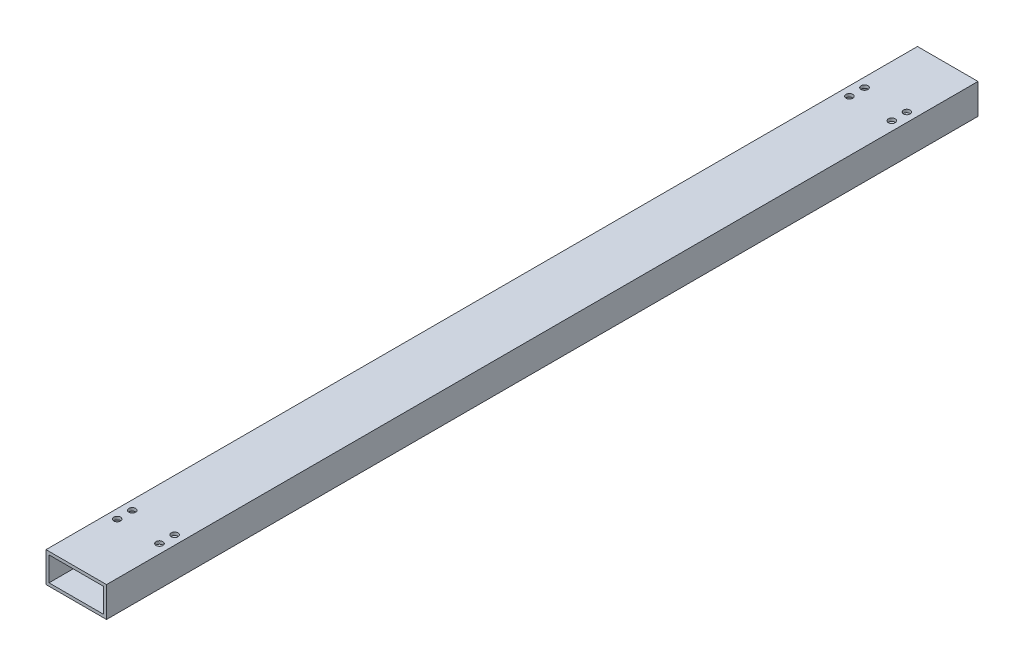
SolidWorks part; units mm, degrees
ref_plane "Front Plane" through (0, 0, 0) normal (0, 0, 1) x (1, 0, 0)
ref_plane "Top Plane" through (0, 0, 0) normal (0, 1, 0) x (1, 0, 0)
ref_plane "Right Plane" through (0, 0, 0) normal (1, 0, 0) x (0, 0, -1)
sketch "Sketch1" plane through (0, 0, 0) normal (0, 0, 1) x (1, 0, 0)
  line L0 (31.75, 0) -> (28.575, 0) construction
  line L1 (-31.75, 0) -> (31.75, 0) construction
  line L2 (0, 15.875) -> (0, -15.875)
  point P7 (0, 0)
  dimension "Width" = 63.5
  dimension "Wall Thickness" = 3.175
  dimension "Height" = 31.75
sketch "Sketch2" plane through (0, 0, 0) normal (1, 0, 0) x (0, 0, -1)
  line L0 (457.2, 0) -> (-457.2, 0)
  point P4 (0, 0)
  dimension "Length" = 914.4
sketch "Sketch3" plane through (0, 0, 0) normal (0, 0, 1) x (1, 0, 0)
  line L0 (0, 12.7) -> (0, 15.875) construction
  line L1 (-31.75, 15.875) -> (31.75, 15.875)
  line L2 (-31.75, 15.875) -> (-31.75, -15.875)
  line L3 (-31.75, -15.875) -> (31.75, -15.875)
  line L4 (31.75, 15.875) -> (31.75, -15.875)
  line L5 (-31.75, 15.875) -> (31.75, -15.875) construction
  line L6 (-31.75, -15.875) -> (31.75, 15.875) construction
  line L7 (-28.575, 12.7) -> (28.575, 12.7)
  line L8 (-28.575, 12.7) -> (-28.575, -12.7)
  line L9 (-28.575, -12.7) -> (28.575, -12.7)
  line L10 (28.575, 12.7) -> (28.575, -12.7)
  line L11 (-28.575, 12.7) -> (28.575, -12.7) construction
  line L12 (-28.575, -12.7) -> (28.575, 12.7) construction
  line L13 (31.75, 0) -> (28.575, 0) construction
  line L14 (31.75, 0) -> (28.575, 0) construction
  point P0 (0, 0)
  point P8 (0, 0)
extrude "Boss-Extrude1" add sketch "Sketch3" along normal up to vertex (457.2 mm away) and the other way up to vertex (457.2 mm away) up to point (0, 0, 457.2) other way up to point (0, 0, -457.2)
sketch "Sketch4" plane through (0, 0, 0) normal (0, 0, 1) x (1, 0, 0)
  line L0 (31.75, -15.875) -> (28.575, -15.875) construction
  line L1 (31.75, -15.875) -> (31.75, 15.875) construction
  line L2 (28.575, -12.7) -> (28.575, 12.7) construction
  line L3 (-31.75, -15.875) -> (31.75, -15.875) construction
sketch "Sketch5" plane through (0, -15.875, 0) normal (0, -1, 0) x (1, 0, 0)
  line L1 (-28.575, 384.175) -> (28.575, 384.175)
  line L2 (-28.575, 384.175) -> (-28.575, 400.05)
  line L3 (-28.575, 400.05) -> (28.575, 400.05)
  line L4 (28.575, 384.175) -> (28.575, 400.05)
  line L5 (-28.575, 384.175) -> (28.575, 400.05) construction
  line L6 (-28.575, 400.05) -> (28.575, 384.175) construction
  line L7 (-31.75, 457.2) -> (31.75, 457.2) construction
  line L8 (-31.75, 0) -> (31.75, 0) construction
  line L9 (-31.75, 457.2) -> (-31.75, -457.2) construction
  line L10 (31.75, 457.2) -> (31.75, -457.2) construction
  circle A0 centre (-22.225, 392.1125) radius 3.5719
  circle A1 centre (22.225, 392.1125) radius 3.5719
  circle A2 centre (22.225, -392.1125) radius 3.5719
  circle A3 centre (-22.225, -392.1125) radius 3.5719
  circle A4 centre (22.225, 376.2375) radius 3.5719
  circle A5 centre (-22.225, 376.2375) radius 3.5719
  circle A6 centre (22.225, -376.2375) radius 3.5719
  circle A7 centre (-22.225, -376.2375) radius 3.5719
  point P0 (0, 392.1125)
  dimension "D3" = 7.1437
  dimension "D4" = 7.1437
  dimension "D1" = 57.15
  dimension "D2" = 15.875
  dimension "D5" = 22.225
  dimension "D6" = 22.225
  dimension "D7" = 44.45
  dimension "D8" = 57.15
  dimension "D9" = 15.875
extrude "Cut-Extrude1" cut sketch "Sketch5" against normal through all contours A0 | A1 | A3 | A2 | A7 | A6 | A4 | A5
